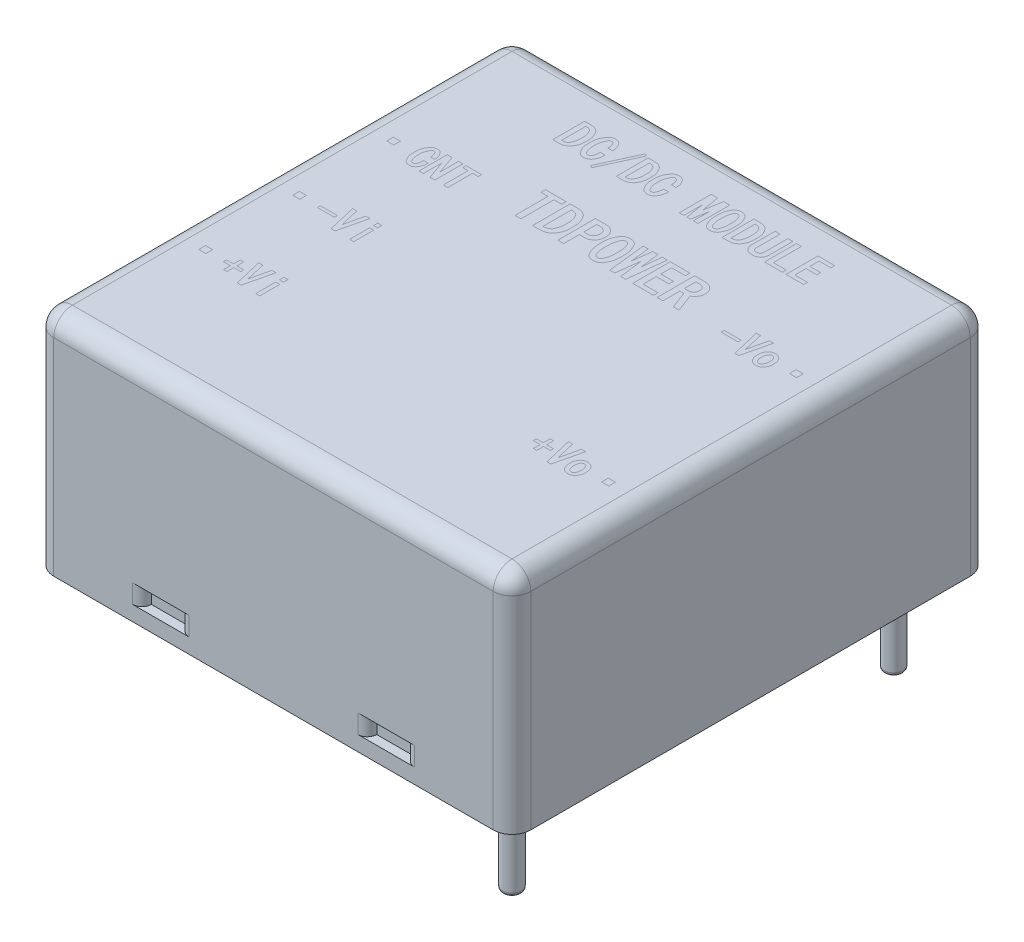
SolidWorks part; units mm, degrees
ref_plane "Спереди" through (0, 0, 0) normal (0, 0, 1) x (1, 0, 0)
ref_plane "Сверху" through (0, 0, 0) normal (0, 1, 0) x (1, 0, 0)
ref_plane "Справа" through (0, 0, 0) normal (1, 0, 0) x (0, 0, -1)
sketch "Эскиз1" plane through (0, 0, 0) normal (0, 1, 0) x (1, 0, 0)
  line L1 (-12.7, 12.7) -> (12.7, 12.7)
  line L2 (-12.7, 12.7) -> (-12.7, -12.7)
  line L3 (-12.7, -12.7) -> (12.7, -12.7)
  line L4 (12.7, 12.7) -> (12.7, -12.7)
  line L5 (-12.7, 12.7) -> (12.7, -12.7) construction
  line L6 (-12.7, -12.7) -> (12.7, 12.7) construction
  point P0 (0, 0)
  dimension "D1" = 25.4
  dimension "D2" = 25.4
extrude "Бобышка-Вытянуть1" add sketch "Эскиз1" along normal blind 12
sketch "Эскиз2" plane through (0, 0, 0) normal (0, -1, 0) x (1, 0, 0)
  line L0 (-12.7, 0) -> (12.7, 0) construction
  line L1 (-12.7, -12.7) -> (-12.7, 12.7) construction
  line L2 (12.7, 12.7) -> (12.7, -12.7) construction
  circle A0 centre (10.16, 10.16) radius 0.75
  circle A1 centre (10.16, -10.16) radius 0.75
  circle A2 centre (-10.16, 2.54) radius 0.75
  circle A3 centre (-10.16, -2.54) radius 0.75
  circle A4 centre (-10.16, -10.16) radius 0.75
  circle A5 centre (10.16, 0) radius 0.75
  point P8 (8.8992, 0)
  point P19 (0, 0)
  dimension "D2" = 1.5
  dimension "D1" = 20.32
  dimension "D3" = 5.08
  dimension "D4" = 7.62
  dimension "D5" = 20.32
  dimension "D6" = 10.16
extrude "Бобышка-Вытянуть2" add sketch "Эскиз2" along normal blind 0.8
sketch "Эскиз3" plane through (0, -0.8, 0) normal (0, -1, 0) x (1, 0, 0)
  circle A0 centre (10.16, 10.16) radius 0.5
  circle A1 centre (10.16, 0) radius 0.5 construction
  circle A2 centre (10.16, -10.16) radius 0.5
  circle A3 centre (-10.16, 2.54) radius 0.5
  circle A4 centre (-10.16, -2.54) radius 0.5
  circle A5 centre (-10.16, -10.16) radius 0.5
  dimension "D1" = 1
extrude "Бобышка-Вытянуть3" add sketch "Эскиз3" along normal blind 4
fillet "Скругление1" radius 0.2 5 edges at (-10.16, -4.8, 2.04) (10.16, -4.8, -10.66) (10.16, -4.8, 9.66) (-10.16, -4.8, -10.66) (-10.16, -4.8, -3.04)
fillet "Скругление2" radius 1 8 edges at (0, 12, 12.7) (-12.7, 12, 0) (0, 12, -12.7) (12.7, 12, 0) (12.7, 6, 12.7) (-12.7, 6, 12.7) (12.7, 6, -12.7) (-12.7, 6, -12.7)
sketch "Эскиз4" plane through (0, 12, 0) normal (0, 1, 0) x (1, 0, 0)
  line L0 (-11.7, 8.7) -> (11.7, 8.7) construction
  line L1 (-11.7, 11.7) -> (-11.7, -11.7) construction
  line L2 (11.7, -11.7) -> (11.7, 11.7) construction
  line L3 (-11.7, 12.7) -> (11.7, 12.7) construction
  line L4 (-11.7, 3.7) -> (0, 3.7) construction
  line L5 (-11.7, -1.3) -> (0, -1.3) construction
  line L6 (-11.7, -6.3) -> (0, -6.3) construction
  line L7 (0, 3.7) -> (11.7, 3.7) construction
  line L8 (0, -1.3) -> (11.7, -1.3) construction
  line L9 (0, -6.3) -> (11.7, -6.3) construction
  line L10 (-11.7, 4.2) -> (11.7, 4.2) construction
  text T0 "<b>DC/DC MODULE</b>" font "MS Gothic" height 1.7
  text T1 "<b>・CNT</b>" font "MS Gothic" height 1.5
  text T2 "<b>・-Vin</b>" font "MS Gothic" height 1.5
  text T3 "<b>・+Vin</b>" font "MS Gothic" height 1.5
  text T4 "<b>-Vo・</b>" font "MS Gothic" height 1.5
  text T5 "<b>+Vo・</b>" font "MS Gothic" height 1.5
  text T6 "<b>TDPOWER</b>" font "MS Gothic" height 2
  dimension "D1" = 4
  dimension "D2" = 5
  dimension "D3" = 5
  dimension "D4" = 5
  dimension "D5" = 0.5
wrap "Перенос1" sketch "Эскиз4" wrap type scribe source sketch "Эскиз4"
sketch "Эскиз5" plane through (0, 0, 12.7) normal (0, 0, 1) x (1, 0, 0)
  line L0 (0, 0) -> (0, 12) construction
  line L2 (7, 0.8) -> (5, 0.8)
  line L3 (-7, 1.8) -> (-5, 1.8)
  line L4 (-7, 1.8) -> (-7, 0.8)
  line L5 (-7, 0.8) -> (-5, 0.8)
  line L6 (-5, 1.8) -> (-5, 0.8)
  line L7 (5, 1.8) -> (5, 0.8)
  line L8 (7, 1.8) -> (5, 1.8)
  line L9 (7, 1.8) -> (7, 0.8)
  line L10 (-11.7, 0) -> (11.7, 0) construction
  dimension "D1" = 10
  dimension "D2" = 2
  dimension "D3" = 1
  dimension "D4" = 0.8
extrude "Вырез-Вытянуть2" cut sketch "Эскиз5" against normal blind 0.5
mirror "Зеркальное отражение3" about plane through (0, 0, 0) normal (0, 0, 1) of "Вырез-Вытянуть2"
fillet "Скругление4" radius 0.5 8 edges at (-7, 1.3, -12.7) (-5, 1.3, -12.7) (5, 1.3, -12.7) (7, 1.3, -12.7) (7, 1.3, 12.7) (5, 1.3, 12.7) (-7, 1.3, 12.7) (-5, 1.3, 12.7)
